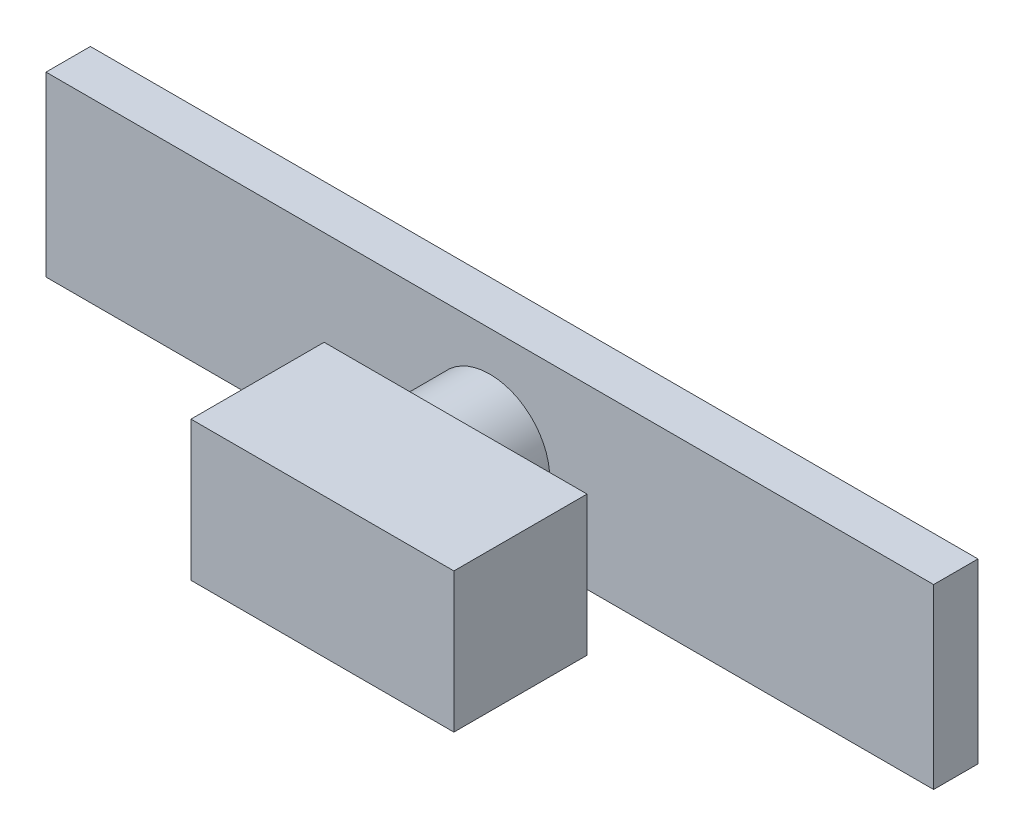
SolidWorks part; units mm, degrees
ref_plane "Front Plane" through (0, 0, 0) normal (0, 0, 1) x (1, 0, 0)
ref_plane "Top Plane" through (0, 0, 0) normal (0, 1, 0) x (1, 0, 0)
ref_plane "Right Plane" through (0, 0, 0) normal (1, 0, 0) x (0, 0, -1)
sketch "Sketch2" plane through (0, 0, 0) normal (0, 0, 1) x (1, 0, 0)
  line L1 (-47.8692, 21.2481) -> (206.1308, 21.2481)
  line L2 (-47.8692, 21.2481) -> (-47.8692, 8.5481)
  line L3 (-47.8692, 8.5481) -> (206.1308, 8.5481)
  line L4 (206.1308, 21.2481) -> (206.1308, 8.5481)
  dimension "D1" = 12.7
  dimension "D2" = 254
extrude "Boss-Extrude1" add sketch "Sketch2" along normal blind 50.8
sketch "Sketch3" plane through (0, 21.2481, 0) normal (0, 1, 0) x (1, 0, 0)
  circle A0 centre (79.1308, -28.4831) radius 17.1408
extrude "Boss-Extrude2" add sketch "Sketch3" along normal blind 19.05
sketch "Sketch4" plane through (0, 40.2981, 0) normal (0, 1, 0) x (1, 0, 0)
  line L1 (50.7675, -8.111) -> (126.0034, -8.111)
  line L2 (50.7675, -8.111) -> (50.7675, -48.0661)
  line L3 (50.7675, -48.0661) -> (126.0034, -48.0661)
  line L4 (126.0034, -8.111) -> (126.0034, -48.0661)
extrude "Boss-Extrude3" add sketch "Sketch4" along normal blind 38.1
scale "Scale2" scale about centroid uniform scaling yes scale factor 0.06
move or copy body "rotate" bodies to move or copy 105 copy no rotation origin (0, 33.6669, 26.5501) rotation axis (1, 0, 0) rotation angle 90
scale "Scale5" scale about centroid uniform scaling yes scale factor 0.25
move or copy body "-4 x" bodies to move or copy 111 copy no translate (-101.6, 0, 0)
move or copy body "-2 y" bodies to move or copy 117 copy no translate (0, -50.8, 0)
scale "Scale6" bodies to scale 121 scale about centroid uniform scaling yes scale factor 0.25
move or copy body "-2.1z" bodies to move or copy 122 copy no translate (0, 0, -30.48)
